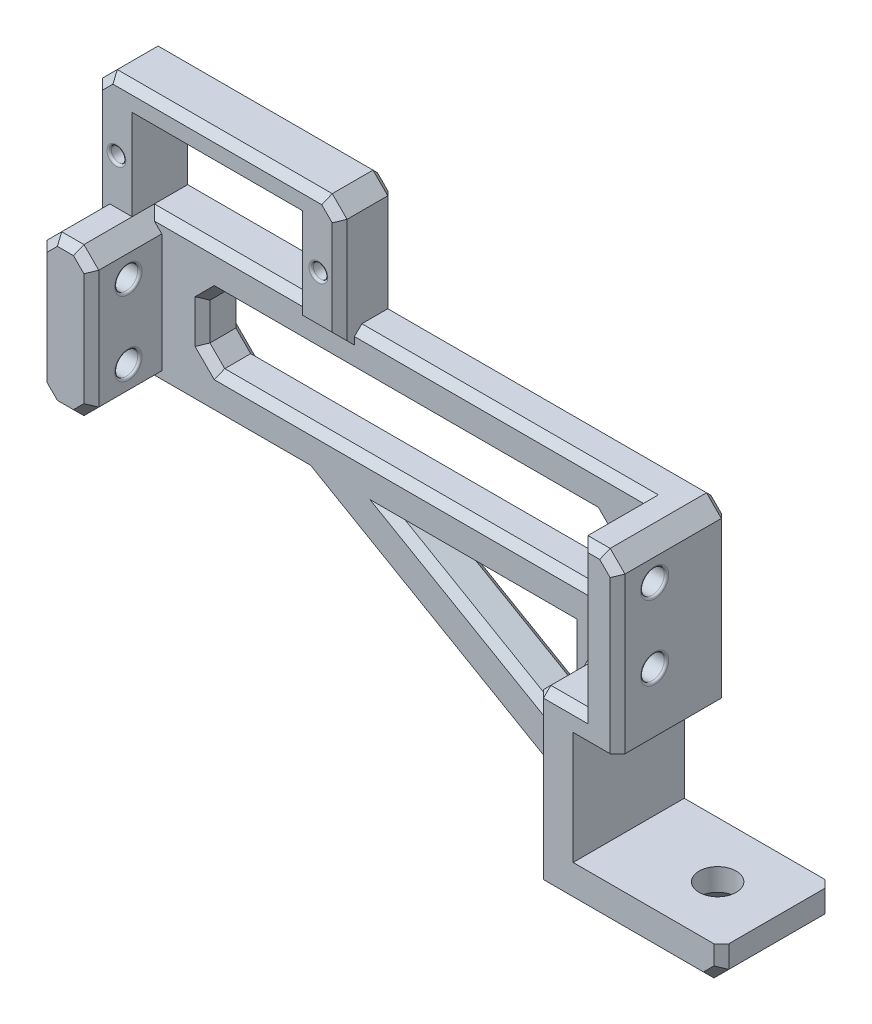
SolidWorks part; units mm, degrees
ref_plane "Plano frontal" through (0, 0, 0) normal (0, 0, 1) x (1, 0, 0)
ref_plane "Plano superior" through (0, 0, 0) normal (0, 1, 0) x (1, 0, 0)
ref_plane "Plano direito" through (0, 0, 0) normal (1, 0, 0) x (0, 0, -1)
sketch "Esboço1" plane through (0, 0, 0) normal (0, 0, 1) x (1, 0, 0)
  line L0 (0, 0) -> (-6, 0)
  line L1 (-6, 0) -> (-6, -15.2)
  line L2 (-6, -15.2) -> (14, -15.2)
  line L3 (14, -15.2) -> (14, -20.2)
  line L4 (14, -20.2) -> (-11, -20.2)
  line L5 (-11, -20.2) -> (-11, 3)
  line L6 (-11, 3) -> (0, 3)
  line L7 (0, 3) -> (0, 0)
  dimension "D1" = 15.2
  dimension "D2" = 6
  dimension "D3" = 20
  dimension "D4" = 5
  dimension "D5" = 3
  dimension "D6" = 5
extrude "Ressalto-extrusão1" add sketch "Esboço1" along normal mid plane 15
ref_plane "Plano3" through (0, 0, -3) normal (0, 0, -1) x (-1, 0, 0)
sketch "Esboço2" plane through (0, 0, -3) normal (0, 0, 1) x (1, 0, 0)
  line L1 (-78, 38.2) -> (-45, 38.2)
  line L2 (-73, 35.2) -> (-73, 23)
  line L3 (-73, 35.2) -> (-50, 35.2)
  line L4 (-50, 35.2) -> (-50, 23)
  line L5 (-73, 23) -> (-50, 23)
  line L6 (-73, 35.2) -> (-50, 23) construction
  line L7 (-50, 35.2) -> (-73, 23) construction
  line L11 (-78, 38.2) -> (-78, 20)
  line L12 (-78, 20) -> (-45, 20)
  line L13 (-45, 38.2) -> (-45, 20)
  line L14 (-11, 3) -> (-11, -20.2) construction
  line L16 (0, 3) -> (-11, 3) construction
  circle A0 centre (-75.125, 29.1) radius 0.975
  circle A1 centre (-47.875, 29.1) radius 0.975
  point P2 (-61.5, 29.1)
  point P13 (-45, 29.1)
  dimension "D3" = 1.95
  dimension "D4" = 1.95
  dimension "D1" = 12.2
  dimension "D2" = 23
  dimension "D5" = 3
  dimension "D6" = 3
  dimension "D7" = 27.25
  dimension "D8" = 13.625
  dimension "D9" = 5
  dimension "D10" = 5
  dimension "D11" = 17
  dimension "D12" = 34
extrude "Ressalto-extrusão2" add sketch "Esboço2" along normal blind 3 separate body
sketch "Esboço3" plane through (0, 0, 0) normal (0, 0, 1) x (1, 0, 0)
  line L0 (-73, 35.2) -> (-73, 23) construction
  line L1 (-75.125, 31.5537) -> (-77.25, 30.3269)
  line L2 (-77.25, 30.3269) -> (-77.25, 27.8731)
  line L3 (-77.25, 27.8731) -> (-75.125, 26.6463)
  line L4 (-75.125, 26.6463) -> (-73, 27.8731)
  line L5 (-73, 27.8731) -> (-73, 30.3269)
  line L6 (-73, 30.3269) -> (-75.125, 31.5537)
  line L7 (-47.875, 31.5537) -> (-50, 30.3269)
  line L8 (-50, 30.3269) -> (-50, 27.8731)
  line L9 (-50, 27.8731) -> (-47.875, 26.6463)
  line L10 (-47.875, 26.6463) -> (-45.75, 27.8731)
  line L11 (-45.75, 27.8731) -> (-45.75, 30.3269)
  line L12 (-45.75, 30.3269) -> (-47.875, 31.5537)
  line L13 (-50, 23) -> (-50, 35.2) construction
  circle A0 centre (-75.125, 29.1) radius 2.125 construction
  circle A1 centre (-47.875, 29.1) radius 2.125 construction
  circle A2 centre (-47.875, 29.1) radius 0.975 construction
  circle A3 centre (-75.125, 29.1) radius 0.975 construction
  circle A4 centre (-47.875, 29.1) radius 0.975
  circle A5 centre (-75.125, 29.1) radius 0.975
  dimension "D1" = 0
  dimension "D2" = 0
extrude "Ressalto-extrusão3" add sketch "Esboço3" against normal blind 6
sketch "Esboço4" plane through (0, 0, -6) normal (0, 0, -1) x (-1, 0, 0)
  line L6 (47.875, 31.5537) -> (45.75, 30.3269)
  line L7 (45.75, 30.3269) -> (45.75, 27.8731)
  line L8 (45.75, 27.8731) -> (47.875, 26.6463)
  line L9 (47.875, 26.6463) -> (50, 27.8731)
  line L10 (50, 27.8731) -> (50, 30.3269)
  line L11 (50, 30.3269) -> (47.875, 31.5537)
  line L12 (47.875, 31.5537) -> (45.75, 30.3269)
  line L13 (45.75, 30.3269) -> (45.75, 27.8731)
  line L14 (45.75, 27.8731) -> (47.875, 26.6463)
  line L15 (47.875, 26.6463) -> (50, 27.8731)
  line L16 (50, 27.8731) -> (50, 30.3269)
  line L17 (50, 30.3269) -> (47.875, 31.5537)
  line L18 (75.125, 31.5537) -> (73, 30.3269)
  line L19 (73, 30.3269) -> (73, 27.8731)
  line L20 (73, 27.8731) -> (75.125, 26.6463)
  line L21 (75.125, 26.6463) -> (77.25, 27.8731)
  line L22 (77.25, 27.8731) -> (77.25, 30.3269)
  line L23 (77.25, 30.3269) -> (75.125, 31.5537)
  line L24 (75.125, 31.5537) -> (73, 30.3269)
  line L25 (73, 30.3269) -> (73, 27.8731)
  line L26 (73, 27.8731) -> (75.125, 26.6463)
  line L27 (75.125, 26.6463) -> (77.25, 27.8731)
  line L28 (77.25, 27.8731) -> (77.25, 30.3269)
  line L29 (77.25, 30.3269) -> (75.125, 31.5537)
  dimension "D1" = 0
  dimension "D2" = 0
extrude "Ressalto-extrusão4" add sketch "Esboço4" along normal blind 1.5
sketch "Esboço6" plane through (0, -20.2, 0) normal (0, -1, 0) x (1, 0, 0)
  line L0 (14, 7.5) -> (14, -7.5) construction
  circle A0 centre (6, 0) radius 2.5
  dimension "D1" = 5
  dimension "D2" = 8
extrude "Corte-extrusão1" cut sketch "Esboço6" against normal blind 9.5
chamfer "Chanfro1" distance 2 angle 45 1 edges at (8.5, -20.2, 0)
ref_plane "Plano1" through (-45.5, 0, 0) normal (-1, 0, 0) x (0, 0, 1)
sketch "Esboço7" plane through (0, 0, 0) normal (1, 0, 0) x (0, 0, -1)
  line L1 (7.5, 3) -> (-7.5, 3)
  line L2 (7.5, 3) -> (7.5, 23)
  line L3 (7.5, 23) -> (-7.5, 23)
  line L4 (-7.5, 3) -> (-7.5, 23)
  circle A1 centre (-2.5, 18) radius 1.6
  circle A2 centre (-2.5, 8) radius 1.6
  dimension "D1" = 3.2
  dimension "D2" = 3.2
  dimension "D3" = 10
  dimension "D4" = 5
  dimension "D5" = 10
  dimension "D6" = 10
  dimension "D7" = 5
  dimension "D8" = 5
extrude "Ressalto-extrusão5" add sketch "Esboço7" against normal blind 5
ref_plane "Plano2" through (-78, 0, 0) normal (1, 0, 0) x (0, 0, -1)
sketch "Esboço9" plane through (-78, 0, 0) normal (1, 0, 0) x (0, 0, -1)
  line L5 (-7.5, 0) -> (-7.5, 23) construction
  line L21 (-7.5, 23) -> (4.5, 23)
  line L22 (-7.5, 23) -> (-7.5, 3)
  line L23 (-7.5, 3) -> (4.5, 3)
  line L25 (4.5, 23) -> (4.5, 3)
  circle A0 centre (-2.5, 8) radius 1.6 construction
  circle A2 centre (-2.5, 18) radius 1.6 construction
  dimension "D2" = 5
  dimension "D3" = 0
  dimension "D1" = 5
extrude "Ressalto-extrusão6" add sketch "Esboço9" along normal blind 2
sketch "Esboço10" plane through (-76, 0, 0) normal (1, 0, 0) x (0, 0, -1)
  line L18 (4.5, 23) -> (4.5, 3)
  line L19 (-7.5, 23) -> (-7.5, 3)
  line L21 (4.5, 23) -> (-7.5, 23)
  line L23 (-7.5, 3) -> (4.5, 3)
  line L24 (4.5, 23) -> (4.5, 3) construction
  circle A0 centre (-2.5, 18) radius 1.6 construction
  circle A2 centre (-2.5, 18) radius 1.6 construction
  circle A4 centre (-2.5, 8) radius 1.6 construction
  circle A5 centre (-2.5, 8) radius 1.6 construction
  circle A6 centre (-2.5, 18) radius 1.55
  circle A7 centre (-2.5, 8) radius 1.55
  dimension "D2" = 0.05
  dimension "D3" = 0.05
  dimension "D1" = 10
  dimension "D4" = 5
  dimension "D5" = 5
  dimension "D6" = 5
  dimension "D8" = 5
extrude "Ressalto-extrusão7" add sketch "Esboço10" along normal blind 5
sketch "Esboço12" plane through (-78, 0, 0) normal (1, 0, 0) x (0, 0, -1)
  line L0 (4.5, 3) -> (7.5, 3)
  line L19 (4.5, 23) -> (4.5, 3)
  line L20 (7.5, 23) -> (7.5, 3)
  line L21 (4.5, 23) -> (7.5, 23)
  line L22 (4.5, 23) -> (3, 23) construction
  line L23 (-7.5, 3) -> (4.5, 3) construction
extrude "Ressalto-extrusão11" add sketch "Esboço12" along normal up to surface (73 mm away) up to face at (-5, 19.6, 2.5)
sketch "Esboço17" plane through (0, 0, 0) normal (0, 0, 1) x (1, 0, 0)
  line L0 (-5, 23) -> (-71, 23) construction
  line L1 (-71, 23) -> (-45, 23)
  line L2 (-71, 23) -> (-71, 20)
  line L3 (-71, 20) -> (-45, 20)
  line L4 (-45, 23) -> (-45, 20)
  line L5 (-71, 23) -> (-71, 3) construction
  line L6 (-71, 20) -> (-45, 20) construction
  line L7 (-45, 20) -> (-45, 38.2) construction
extrude "Corte-extrusão2" cut sketch "Esboço17" against normal up to surface (4.5 mm away) up to face at (-32.6, 11, -4.5)
sketch "Esboço18" plane through (0, 0, -3) normal (0, 0, -1) x (-1, 0, 0)
  line L20 (45, 38.2) -> (45, 23)
  line L21 (45, 23) -> (50, 23)
  line L22 (50, 23) -> (50, 27.8731)
  line L23 (50, 27.8731) -> (47.875, 26.6463)
  line L24 (47.875, 26.6463) -> (45.75, 27.8731)
  line L25 (45.75, 27.8731) -> (45.75, 30.3269)
  line L26 (45.75, 30.3269) -> (47.875, 31.5537)
  line L27 (47.875, 31.5537) -> (50, 30.3269)
  line L28 (50, 30.3269) -> (50, 35.2)
  line L29 (50, 35.2) -> (73, 35.2)
  line L30 (73, 35.2) -> (73, 30.3269)
  line L31 (73, 30.3269) -> (75.125, 31.5537)
  line L32 (75.125, 31.5537) -> (77.25, 30.3269)
  line L33 (77.25, 30.3269) -> (77.25, 27.8731)
  line L34 (77.25, 27.8731) -> (75.125, 26.6463)
  line L35 (75.125, 26.6463) -> (73, 27.8731)
  line L36 (73, 27.8731) -> (73, 23)
  line L37 (73, 23) -> (78, 23)
  line L38 (78, 23) -> (78, 38.2)
  line L39 (78, 38.2) -> (45, 38.2)
  line L40 (45, 38.2) -> (45, 23)
  line L41 (45, 23) -> (50, 23)
  line L42 (50, 23) -> (50, 30.3269)
  line L48 (50, 30.3269) -> (50, 35.2)
  line L49 (50, 35.2) -> (73, 35.2)
  line L50 (73, 35.2) -> (73, 30.3269)
  line L56 (73, 30.3269) -> (73, 23)
  line L58 (78, 23) -> (78, 38.2)
  line L59 (78, 38.2) -> (45, 38.2)
  line L64 (73, 23) -> (78, 23)
  circle A0 centre (75.125, 29.1) radius 0.975 construction
  circle A1 centre (47.875, 29.1) radius 0.975 construction
  circle A2 centre (75.125, 29.1) radius 0.975
  circle A3 centre (47.875, 29.1) radius 0.975
  dimension "D1" = 0
extrude "Ressalto-extrusão14" add sketch "Esboço18" along normal up to surface (4.5 mm away) up to face at (-16.2, -1.88, -7.5)
sketch "Esboço19" plane through (0, 0, -4.5) normal (0, 0, 1) x (1, 0, 0)
  line L0 (-71, 13) -> (-5, 13) construction
  line L1 (-71, 3) -> (-71, 23) construction
  line L2 (-5, 23) -> (-5, 3) construction
  line L3 (-11, 3) -> (-71, 3) construction
  line L4 (-10.5, 8.5) -> (-65.5, 8.5)
  line L5 (-10.5, 8.5) -> (-10.5, 17.5)
  line L6 (-10.5, 17.5) -> (-65.5, 17.5)
  line L7 (-65.5, 8.5) -> (-65.5, 17.5)
  line L8 (-10.5, 8.5) -> (-65.5, 17.5) construction
  line L9 (-10.5, 17.5) -> (-65.5, 8.5) construction
  point P6 (-38, 13)
  dimension "D1" = 5.5
  dimension "D2" = 55
extrude "Corte-extrusão3" cut sketch "Esboço19" against normal blind 10 contours L5 L4 L7 L6
chamfer "Chanfro5" distance 2 angle 45 4 edges at (-65.5, 8.5, -6) (-65.5, 17.5, -6) (-10.5, 8.5, -6) (-10.5, 17.5, -6)
sketch "Esboço20" plane through (0, 0, -7.5) normal (0, 0, -1) x (-1, 0, 0)
  line L0 (11, -20.2) -> (52.8723, 3.975)
  line L1 (11, 3) -> (11, -20.2) construction
  line L2 (11, -20.2) -> (11, 3)
  line L5 (16, -10.385) -> (40.368, 3.6838)
  line L8 (16, 3.1164) -> (16, -10.385)
  line L10 (17, -3.2628) -> (27.5524, -3.7153) construction
  line L11 (17, -9.8077) -> (27.5524, -3.7153) construction
  line L12 (17, -9.8077) -> (17, -3.2628) construction
  line L14 (11, 3) -> (48.4055, 1.3961) construction
  line L17 (11, -20.2) -> (48.4055, 1.3961) construction
  line L19 (11, 3) -> (16, 3.1164)
  line L21 (40.368, 3.6838) -> (52.8723, 3.975)
  dimension "D1" = 60
  dimension "D3" = 5
  dimension "D2" = 6
extrude "Ressalto-extrusão15" add sketch "Esboço20" against normal blind 3
sketch "Esboço21" plane through (0, 0, -4.5) normal (0, 0, 1) x (1, 0, 0)
  line L0 (-16, -10.385) -> (-16, 3) construction
  line L1 (-39.1836, 3) -> (-16, -10.385) construction
  line L2 (-16, 3) -> (-39.1836, 3) construction
  line L3 (-12.5, 17.5) -> (-10.5, 15.5) construction
  line L4 (-10.5, 10.5) -> (-10.5, 15.5) construction
  line L5 (-10.5, 10.5) -> (-12.5, 8.5) construction
  line L6 (-12.5, 8.5) -> (-63.5, 8.5) construction
  line L7 (-63.5, 8.5) -> (-65.5, 10.5) construction
  line L8 (-65.5, 10.5) -> (-65.5, 15.5) construction
  line L9 (-65.5, 15.5) -> (-63.5, 17.5) construction
  line L10 (-12.5, 17.5) -> (-63.5, 17.5) construction
  line L11 (-16, -10.385) -> (-16, 3)
  line L12 (-5, 23) -> (-45, 23)
  line L16 (-5, 23) -> (-45, 23)
  line L18 (-71, 3) -> (-51.1836, 3)
  line L19 (-51.1836, 3) -> (-11, -20.2)
  line L20 (-11, -20.2) -> (-11, 3)
  line L22 (-11, 3) -> (-5, 3)
  line L23 (-5, 3) -> (-5, 23)
  line L30 (-71, 3) -> (-51.1836, 3)
  line L31 (-51.1836, 3) -> (-11, -20.2)
  line L32 (-11, -20.2) -> (-11, 3)
  line L34 (-11, 3) -> (-5, 3)
  line L35 (-5, 3) -> (-5, 23)
  line L36 (-39.1836, 3) -> (-16, -10.385)
  line L37 (-16, 3) -> (-39.1836, 3)
  line L38 (-12.5, 17.5) -> (-10.5, 15.5)
  line L39 (-10.5, 10.5) -> (-10.5, 15.5)
  line L40 (-10.5, 10.5) -> (-12.5, 8.5)
  line L41 (-12.5, 8.5) -> (-63.5, 8.5)
  line L42 (-63.5, 8.5) -> (-65.5, 10.5)
  line L43 (-65.5, 10.5) -> (-65.5, 15.5)
  line L44 (-65.5, 15.5) -> (-63.5, 17.5)
  line L45 (-12.5, 17.5) -> (-63.5, 17.5)
  line L53 (-45, 23) -> (-50, 23)
  line L54 (-45, 23) -> (-50, 23)
  line L56 (-50, 23) -> (-71, 23)
  line L58 (-50, 23) -> (-71, 23)
  line L60 (-71, 23) -> (-71, 3)
  line L61 (-71, 23) -> (-71, 3)
  dimension "D1" = 0
extrude "Ressalto-extrusão16" add sketch "Esboço21" along normal blind 2.5
chamfer "Chanfro8" distance 2 angle 45 2 edges at (-47.5, 23, -2) (-8, 3, -2)
chamfer "Chanfro9" distance 2 angle 45 8 edges at (14, -20.2, 0) (-71, 23, 2.75) (0, 23, 0) (-78, 3, 0) (-78, 23, 3.75) (-78, 38.2, -3.75) (-45, 38.2, -3.75) (-71, 3, 2.75)
chamfer "Chanfro10" distance 1 angle 45 63 edges at (0.5, -20.2, -7.5) (0, 10.5, -7.5) (-45, 29.6, 0) (-11, -8.6, 7.5) (-11, 3, 3.75) (-23.5, 23, -7.5) (0.5, -20.2, 7.5) (-38, 8.5, -7.5) (-65.5, 13, -7.5) (-38, 17.5, -7.5) (-10.5, 13, -7.5) (-64.5, 9.5, -7.5) (-64.5, 16.5, -7.5) (-11.5, 9.5, -7.5) (-11.5, 16.5, -7.5) (-27.5918, 3, -7.5) (-63.5918, 3, -7.5) (-31.0918, -8.6, -7.5) (-27.5918, -3.6925, -7.5) (-16, -3.6925, -7.5) (-25, 23, -2) (-61.5, 23, -2) (-62.0918, 3, -2) (-31.0918, -8.6, -2) (-27.5918, -3.6925, -2) (-16, -3.6925, -2) (-27.5918, 3, -2) (-38, 17.5, -2) (-64.5, 16.5, -2) (-65.5, 13, -2) (-64.5, 9.5, -2) (-38, 8.5, -2) (-11.5, 9.5, -2) (-10.5, 13, -2) (-11.5, 16.5, -2) (-8, 3, 7.5) (-5, 13, 7.5) (-3.5, 23, 7.5) (-78, 20.6, -7.5) (-78, 13, 7.5) (-78, 28.6, 0) (-61.5, 38.2, -7.5) (-45, 29.6, -7.5) (14, -16.7, -7.5) (-1, 22, -7.5) (13, -19.2, -7.5) (-77, 4, -7.5) (-46, 37.2, -7.5) (-77, 37.2, -7.5) (-61.5, 38.2, 0) (-46, 37.2, 0) (-77, 37.2, 0) (-71, 13, 7.5) (-74.5, 3, 7.5) (-74.5, 23, 7.5) (-77, 22, 7.5) (-72, 22, 7.5) (-77, 4, 7.5) (-72, 4, 7.5) (14, -16.7, 7.5) (-1, 22, 7.5) (13, -19.2, 7.5) (0, 10.5, 7.5)
chamfer "Chanfro11" distance 1 angle 45 1 edges at (-11, -20.2, 1.75)
fillet "Filete1" radius 0.3 8 edges at (0, 9.6, 2.5) (-5, 9.6, 2.5) (0, 19.6, 2.5) (-5, 19.6, 2.5) (-71, 8, 0.95) (-71, 18, 0.95) (-46.9, 29.1, 0) (-74.15, 29.1, 0)
